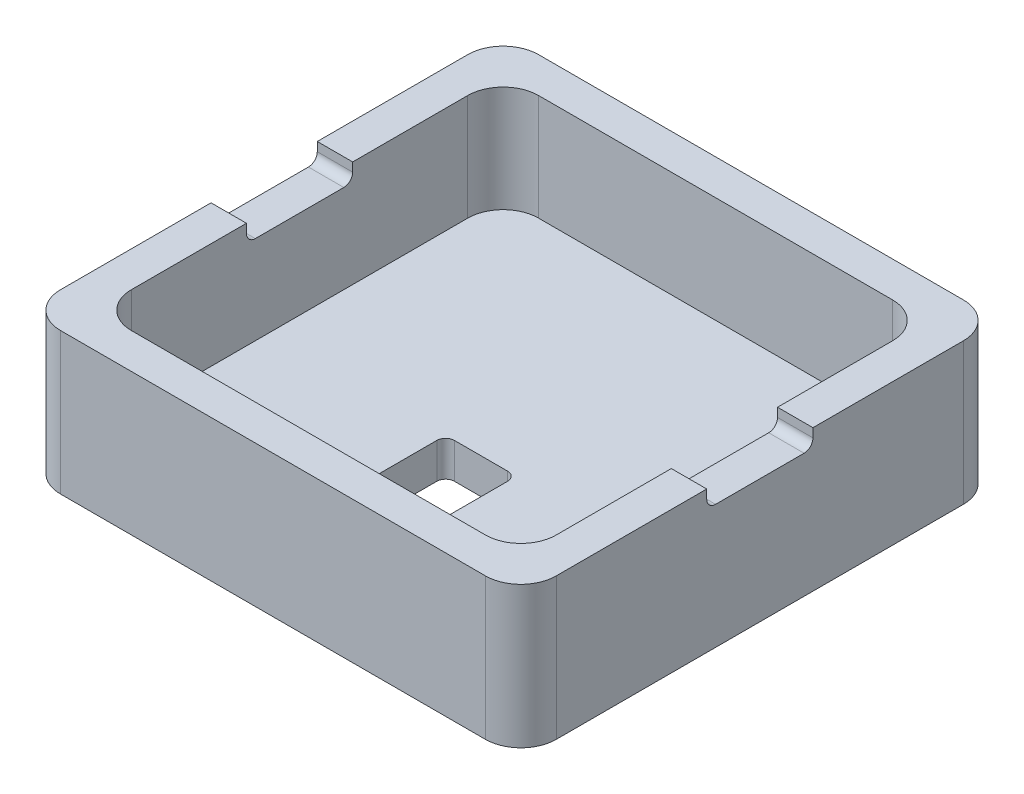
SolidWorks part; units mm, degrees
ref_plane "Front Plane" through (0, 0, 0) normal (0, 0, 1) x (1, 0, 0)
ref_plane "Top Plane" through (0, 0, 0) normal (0, 1, 0) x (1, 0, 0)
ref_plane "Right Plane" through (0, 0, 0) normal (1, 0, 0) x (0, 0, -1)
sketch "Sketch1" plane through (0, 0, 0) normal (0, 1, 0) x (1, 0, 0)
  line L1 (-14, -13.5) -> (14, -13.5)
  line L2 (-14, -13.5) -> (-14, 13.5)
  line L3 (-14, 13.5) -> (14, 13.5)
  line L4 (14, -13.5) -> (14, 13.5)
  line L5 (-14, -13.5) -> (14, 13.5) construction
  line L6 (-14, 13.5) -> (14, -13.5) construction
  point P0 (0, 0)
  dimension "D1" = 28
  dimension "D2" = 27
extrude "Boss-Extrude1" add sketch "Sketch1" along normal blind 2
sketch "Sketch2" plane through (0, 2, 0) normal (0, 1, 0) x (1, 0, 0)
  line L0 (-12, 11.5) -> (-12, -11.5)
  line L1 (-12, -11.5) -> (12, -11.5)
  line L2 (12, -11.5) -> (12, 11.5)
  line L3 (12, 11.5) -> (-12, 11.5)
  line L4 (14, 13.5) -> (-14, 13.5) construction
  line L5 (-14, 13.5) -> (-14, -13.5) construction
  line L6 (-14, -13.5) -> (14, -13.5) construction
  line L7 (14, -13.5) -> (14, 13.5) construction
  line L8 (-14, 13.5) -> (14, 13.5)
  line L9 (14, 13.5) -> (14, -13.5)
  line L10 (14, -13.5) -> (-14, -13.5)
  line L11 (-14, -13.5) -> (-14, 13.5)
  dimension "D1" = 2
  dimension "D2" = 2
  dimension "D3" = 2
  dimension "D4" = 2
extrude "Boss-Extrude2" add sketch "Sketch2" along normal blind 6
sketch "Sketch3" plane through (0, 2, 0) normal (0, 1, 0) x (1, 0, 0)
  line L0 (0, 13.5) -> (0, -13.5) construction
  line L1 (14, 13.5) -> (-14, 13.5) construction
  line L2 (-14, -13.5) -> (14, -13.5) construction
  line L3 (-12, -11.5) -> (12, -11.5) construction
  line L4 (-2, -7.75) -> (2, -7.75)
  line L5 (-2, -7.75) -> (-2, -1.75)
  line L6 (-2, -1.75) -> (2, -1.75)
  line L7 (2, -7.75) -> (2, -1.75)
  line L8 (-2, -7.75) -> (2, -1.75) construction
  line L9 (-2, -1.75) -> (2, -7.75) construction
  point P6 (0, -4.75)
  dimension "D1" = 6
  dimension "D2" = 4
  dimension "D3" = 3.75
extrude "Cut-Extrude1" cut sketch "Sketch3" against normal through all
fillet "Fillet1" radius 2 8 edges at (-12, 5, -11.5) (12, 5, -11.5) (12, 5, 11.5) (-12, 5, 11.5) (14, 4, -13.5) (-14, 4, -13.5) (14, 4, 13.5) (-14, 4, 13.5)
fillet "Fillet2" radius 0.5 4 edges at (2, 1, 7.75) (-2, 1, 7.75) (-2, 1, 1.75) (2, 1, 1.75)
sketch "Sketch4" plane through (14, 0, 0) normal (1, 0, 0) x (0, 0, -1)
  line L0 (0, 0) -> (0, 8) construction
  line L1 (-11.5, 0) -> (11.5, 0) construction
  line L2 (-11.5, 8) -> (11.5, 8) construction
  line L3 (-3, 8) -> (-3, 7)
  line L4 (-3, 7) -> (3, 7)
  line L5 (3, 8) -> (3, 7)
  line L6 (-3, 8) -> (3, 8)
  point P10 (0, 7)
  dimension "D1" = 1
  dimension "2,5" = 3
extrude "Cut-Extrude2" cut sketch "Sketch4" against normal up to surface (2 mm away) up to face at (12, 5, 0)
mirror "Mirror1" about plane through (0, 0, 0) normal (1, 0, 0) of "Cut-Extrude2"
fillet "Fillet3" radius 0.5 4 edges at (13, 7, 3) (13, 7, -3) (-13, 7, 3) (-13, 7, -3)
